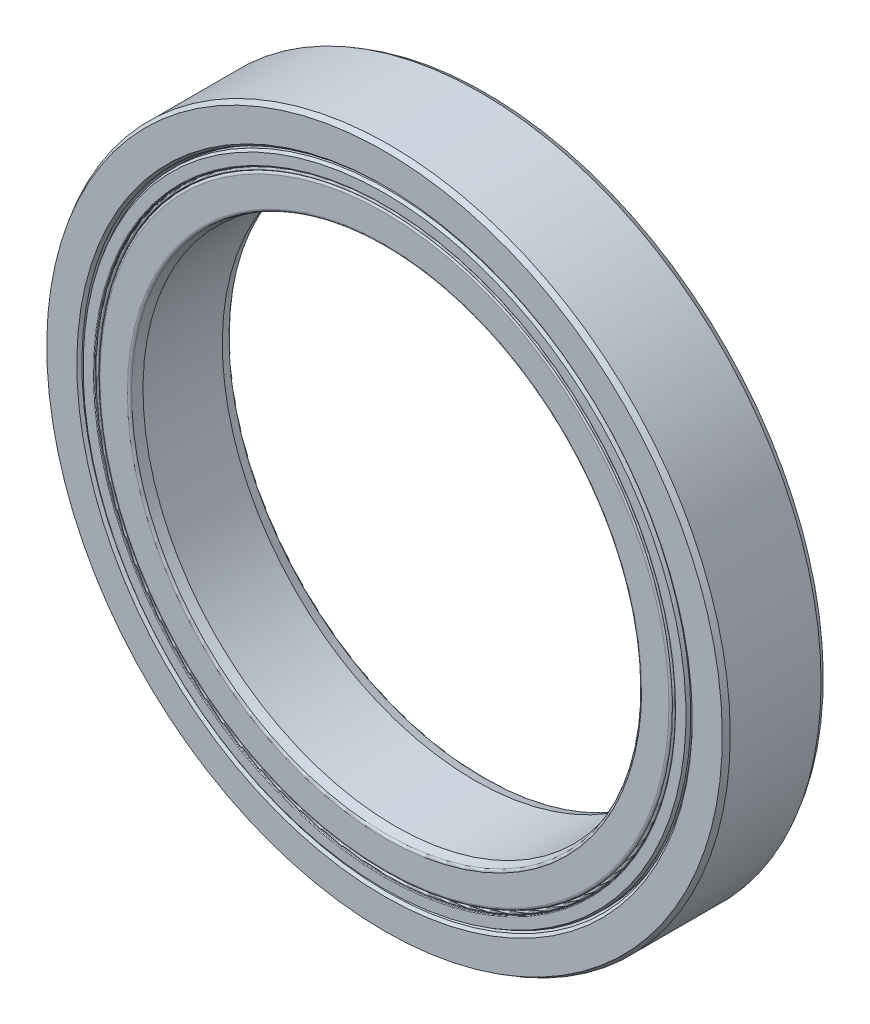
SolidWorks part; units mm, degrees
ref_plane "Front Plane" through (0, 0, 0) normal (0, 0, 1) x (1, 0, 0)
ref_plane "Top Plane" through (0, 0, 0) normal (0, 1, 0) x (1, 0, 0)
ref_plane "Right Plane" through (0, 0, 0) normal (1, 0, 0) x (0, 0, -1)
sketch "Sketch1" plane through (0, 0, 0) normal (0, 0, 1) x (1, 0, 0)
  line L0 (-13.5, 0) -> (13.5, 0) construction
  line L1 (-10, 0) -> (10, 0) construction
  circle A0 centre (0, 0) radius 10 construction
  circle A1 centre (0, 0) radius 13.5 construction
  point P3 (0, 0)
  point P6 (0, 0)
  point P7 (0, -10)
  point P11 (0, -13.5)
  point P12 (0, 10)
  point P13 (0, 13.5)
  dimension "OD" = 27
  dimension "ID" = 20
sketch "Sketch2" plane through (0, 0, 0) normal (1, 0, 0) x (0, 0, -1)
  line L0 (-2, 13.5) -> (2, 13.5) construction
  line L1 (0, 13.5) -> (0, -13.5) construction
  line L2 (1.8, 13.5) -> (-1.8, 13.5)
  line L3 (-1.8, 13.5) -> (-2, 13.3845)
  line L4 (-2, 13.3845) -> (-2, 12.194)
  line L5 (-1.683, 12.015) -> (-1.2723, 12.015)
  line L6 (1.683, 12.015) -> (1.2723, 12.015)
  line L7 (2, 13.3845) -> (2, 12.194)
  line L8 (1.8, 13.5) -> (2, 13.3845)
  line L9 (-1.2723, 12.015) -> (-1.2723, 12.51) construction
  line L10 (-1.2723, 12.51) -> (-1.2723, 13.005) construction
  line L11 (0, 13.5) -> (0, -13.5) construction
  line L12 (-2, 0) -> (2, 0) construction
  line L13 (2, 10) -> (-2, 10) construction
  line L14 (-2, 10) -> (-2, -10) construction
  line L15 (-2, -10) -> (2, -10) construction
  line L16 (2, 13.5) -> (2, -13.5) construction
  line L17 (-1.2723, 13.005) -> (-1.2723, 13.5) construction
  line L18 (-1.2723, 13.005) -> (0, 13.005) construction
  line L20 (-1.683, 12.015) -> (-1.9, 12.094)
  line L21 (-1.9, 12.094) -> (-2, 12.194)
  line L26 (1.9, 12.094) -> (2, 12.194)
  line L27 (1.683, 12.015) -> (1.9, 12.094)
  arc A0 (-1.2723, 12.015) -> (1.2723, 12.015) centre (0, 11.6925) cw
  circle A1 centre (0, 11.6925) radius 1.3125 construction
  point P17 (0, 0)
  point P21 (0, 13.5)
  point P30 (0, -10)
  dimension "Approx. Ball Dia." = 2.625
  dimension "Width" = 4
  dimension "For Shaft Diameter" = 20
  dimension "For Housing ID" = 27
  dimension "D4" = 24.03
  dimension "D2" = 20
  dimension "D5" = 45
  dimension "D1" = 30
  dimension "D6" = 0.2
  dimension "D7" = 0.1
sketch "Sketch3" plane through (0, 0, 0) normal (1, 0, 0) x (0, 0, -1)
  line L14 (-1.683, 12.015) -> (-1.9, 12.094) construction
  line L15 (-1.9, 12.094) -> (-2, 12.194) construction
  line L16 (-2, 13.3845) -> (-2, 12.194) construction
  line L17 (-1.8, 13.5) -> (-2, 13.3845) construction
  line L18 (1.8, 13.5) -> (-1.8, 13.5) construction
  line L19 (1.8, 13.5) -> (2, 13.3845) construction
  line L20 (2, 13.3845) -> (2, 12.194) construction
  line L21 (1.9, 12.094) -> (2, 12.194) construction
  line L22 (1.683, 12.015) -> (1.9, 12.094) construction
  line L23 (1.683, 12.015) -> (1.2723, 12.015) construction
  line L24 (-1.683, 12.015) -> (-1.2723, 12.015) construction
  line L25 (-1.683, 12.015) -> (-1.9, 12.094)
  line L26 (-1.9, 12.094) -> (-2, 12.194)
  line L27 (-2, 13.3845) -> (-2, 12.194)
  line L28 (-1.8, 13.5) -> (-2, 13.3845)
  line L29 (1.8, 13.5) -> (-1.8, 13.5)
  line L30 (1.8, 13.5) -> (2, 13.3845)
  line L31 (2, 13.3845) -> (2, 12.194)
  line L32 (1.9, 12.094) -> (2, 12.194)
  line L33 (1.683, 12.015) -> (1.9, 12.094)
  line L34 (1.683, 12.015) -> (1.2723, 12.015)
  line L35 (-1.683, 12.015) -> (-1.2723, 12.015)
  arc A2 (1.2723, 12.015) -> (-1.2723, 12.015) centre (0, 11.6925) ccw construction
  arc A3 (1.2723, 12.015) -> (-1.2723, 12.015) centre (0, 11.6925) ccw
revolve "Revolve1" add sketch "Sketch3" angle 360 about L12
sketch "Sketch4" plane through (0, 0, 0) normal (1, 0, 0) x (0, 0, -1)
  line L0 (0, 13.5) -> (0, -13.5) construction
  line L1 (0, 13.5) -> (0, -13.5) construction
  line L2 (-1.5726, 10) -> (-1.9271, 10.095)
  line L3 (-2, 10.19) -> (-2, 11.2716)
  line L4 (2, -13.3845) -> (2, 13.3845) construction
  line L5 (-1.9016, 11.37) -> (-1.2723, 11.37)
  line L6 (-1.5726, 10) -> (1.5726, 10)
  line L7 (2, 13.3845) -> (2, 12.194) construction
  line L8 (1.5726, 10) -> (1.9271, 10.095)
  line L9 (0, 13.005) -> (0, 10) construction
  line L10 (2, 10.19) -> (2, 11.2716)
  line L11 (1.9016, 11.37) -> (1.2723, 11.37)
  line L12 (1.5726, 10) -> (1.5726, 10.095) construction
  line L13 (1.5726, 10.095) -> (1.5726, 10.19) construction
  line L14 (1.5726, 10.19) -> (1.5726, 10.285) construction
  line L15 (1.5726, 10.285) -> (1.5726, 10.38) construction
  circle A0 centre (0, 11.6925) radius 1.3125 construction
  arc A1 (1.2723, 11.37) -> (-1.2723, 11.37) centre (0, 11.6925) cw
  arc A2 (2, 11.2716) -> (1.9016, 11.37) centre (1.9016, 11.2716) ccw
  arc A3 (-2, 11.2716) -> (-1.9016, 11.37) centre (-1.9016, 11.2716) cw
  arc A4 (1.9271, 10.095) -> (2, 10.19) centre (1.9016, 10.19) ccw
  arc A5 (-1.9271, 10.095) -> (-2, 10.19) centre (-1.9016, 10.19) cw
  point P14 (2, 10.1145)
  point P36 (0, 10.38)
  dimension "D1" = 15
revolve "Revolve2" add sketch "Sketch4" angle 360 about L12
sketch "Sketch5" plane through (0, 0, 0) normal (1, 0, 0) x (0, 0, -1)
  line L0 (-1.3125, 11.6925) -> (1.3125, 11.6925)
  arc A2 (-1.3125, 11.6925) -> (1.3125, 11.6925) centre (0, 11.6925) cw
  arc A3 (1.2723, 12.015) -> (-1.2723, 12.015) centre (0, 11.6925) ccw construction
revolve "Revolve3" add sketch "Sketch5" angle 360 about L0
pattern_circular "CirPattern1" count 18 over 360 about axis through (0, 0, 2) along (0, 0, -1) of bodies 104
sketch "Sketch6" plane through (0, 0, 0) normal (1, 0, 0) x (0, 0, -1)
  line L1 (-1.8788, 12.015) -> (-1.3125, 12.015)
  line L2 (-2, 11.945) -> (-2, 11.538)
  line L3 (-1.972, 11.51) -> (-1.3125, 11.51)
  line L4 (-1.3125, 12.015) -> (-1.3125, 11.51)
  line L5 (-2, 10.19) -> (-2, 11.2716) construction
  line L6 (-1.8, 13.5) -> (-2, 13.3845) construction
  line L7 (0, 13.5) -> (0, 10) construction
  line L8 (1.972, 11.51) -> (1.3125, 11.51)
  line L9 (1.3125, 12.015) -> (1.3125, 11.51)
  line L10 (1.8788, 12.015) -> (1.3125, 12.015)
  line L11 (2, 11.945) -> (2, 11.538)
  line L13 (-1.9016, 11.37) -> (-1.2723, 11.37) construction
  line L14 (-2, 11.945) -> (-1.8788, 12.015)
  line L15 (-1.683, 12.015) -> (-1.2723, 12.015) construction
  line L16 (2, 11.945) -> (1.8788, 12.015)
  arc A0 (-2, 11.538) -> (-1.972, 11.51) centre (-1.972, 11.538) ccw
  circle A1 centre (0, 11.6925) radius 1.3125 construction
  arc A2 (2, 11.538) -> (1.972, 11.51) centre (1.972, 11.538) cw
  point P26 (-2, 11.51)
  dimension "D3" = 0.028
  dimension "D1" = 0.14
  dimension "D2" = 0.07
revolve "Revolve4" add sketch "Sketch6" angle 360 about L12
sketch "Sketch7" plane through (0, 0, 0) normal (1, 0, 0) x (0, 0, -1)
  line L3 (-1.3125, 11.51) -> (-1.8906, 11.51)
  line L4 (-1.972, 11.51) -> (-1.3125, 11.51) construction
  line L7 (0, 10.38) -> (0, 10) construction
  line L8 (0, 13.5) -> (0, -13.5) construction
  line L21 (-1.8906, 11.51) -> (-1.925, 11.5039)
  line L22 (-1.9225, 11.475) -> (-1.9475, 11.475)
  line L23 (-1.9475, 11.37) -> (-1.3125, 11.37)
  line L24 (-1.3125, 11.37) -> (-1.3125, 11.51)
  line L25 (-1.9016, 11.37) -> (-1.2723, 11.37) construction
  line L26 (-2, 11.538) -> (-2, 11.37) construction
  line L27 (-2, 11.37) -> (-1.9475, 11.37) construction
  line L28 (-1.8906, 11.51) -> (-1.8906, 11.475) construction
  line L29 (-1.8906, 11.475) -> (-1.8906, 11.44) construction
  line L30 (-1.8906, 11.44) -> (-1.8906, 11.405) construction
  line L31 (-1.8906, 11.405) -> (-1.8906, 11.37) construction
  circle A2 centre (0, 11.6925) radius 1.3125 construction
  arc A9 (-1.925, 11.5039) -> (-1.9225, 11.475) centre (-1.9225, 11.4896) ccw
  arc A10 (-1.9475, 11.475) -> (-1.9475, 11.37) centre (-1.9475, 11.4225) ccw
  dimension "D1" = 0.025
  dimension "D2" = 10
revolve "Revolve5" add sketch "Sketch7" angle 360 about L12
equation "\"D4@Sketch2\"=\"OD@Sketch1\"*.89"
equation "\"D1@Sketch6\"=(\"OD@Sketch1\"-\"ID@Sketch1\")*.02"
equation "\"D2@Sketch6\"=\"D1@Sketch6\"*.5"
equation "\"D3@Sketch6\"=\"D1@Sketch6\"*.2"
equation "\"D6@Sketch2\"=\"Width@Sketch2\"*.05"
equation "\"D7@Sketch2\"=\"D6@Sketch2\"*.5"
equation "\"D1@CirPattern1\" =  ( pi * \"OD@Sketch1\" )  * .5625 / \"Approx. Ball Dia.@Sketch2\""
equation "\"Approx. Ball Dia.@Sketch2\"=(\"OD@Sketch1\"-\"ID@Sketch1\")*.5*.75"
